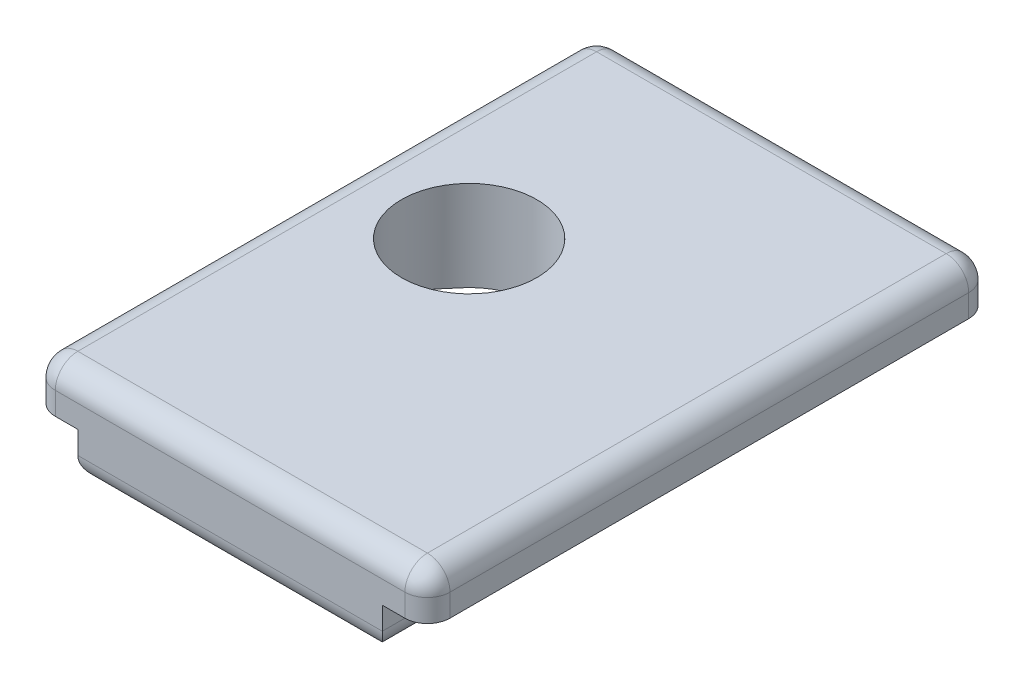
SolidWorks part; units mm, degrees
ref_plane "Front Plane" through (0, 0, 0) normal (0, 0, 1) x (1, 0, 0)
ref_plane "Top Plane" through (0, 0, 0) normal (0, 1, 0) x (1, 0, 0)
ref_plane "Right Plane" through (0, 0, 0) normal (1, 0, 0) x (0, 0, -1)
sketch "Sketch1" plane through (0, 0, 0) normal (0, 1, 0) x (1, 0, 0)
  line L1 (8.75, -12.5) -> (-8.75, -12.5)
  line L2 (8.75, -12.5) -> (8.75, 12.5)
  line L3 (8.75, 12.5) -> (-8.75, 12.5)
  line L4 (-8.75, -12.5) -> (-8.75, 12.5)
  line L5 (8.75, -12.5) -> (-8.75, 12.5) construction
  line L6 (8.75, 12.5) -> (-8.75, -12.5) construction
  point P0 (0, 0)
  dimension "D1" = 17.5
  dimension "D2" = 25
extrude "Boss-Extrude1" add sketch "Sketch1" along normal blind 2
sketch "Sketch2" plane through (0, 0, 0) normal (0, -1, 0) x (1, 0, 0)
  line L0 (-8.75, 12.5) -> (8.75, 12.5) construction
  line L1 (-6.75, 12.5) -> (6.75, 12.5)
  line L2 (-6.75, 12.5) -> (-6.75, -10.5)
  line L3 (-6.75, -10.5) -> (6.75, -10.5)
  line L4 (6.75, 12.5) -> (6.75, -10.5)
  line L5 (8.75, -12.5) -> (-8.75, -12.5) construction
  dimension "D1" = 6.75
  dimension "D2" = 6.75
  dimension "D3" = 2
extrude "Boss-Extrude2" add sketch "Sketch2" along normal blind 2
sketch "Sketch3" plane through (0, 2, 0) normal (0, 1, 0) x (1, 0, 0)
  line L1 (8.75, 12.5) -> (-8.75, 12.5) construction
  line L3 (8.75, -12.5) -> (8.75, 12.5) construction
  circle A0 centre (-3.4, 1.5) radius 3
  dimension "D1" = 6
  dimension "D2" = 11
  dimension "D3" = 12.15
extrude "Cut-Extrude1" cut sketch "Sketch3" against normal through all
fillet "Fillet1" radius 1 12 edges at (8.75, 1, -12.5) (0, 2, -12.5) (-8.75, 1, -12.5) (0, 2, 12.5) (8.75, 2, 0) (-8.75, 2, 0) (6.75, -2, 1) (0, -2, -10.5) (-6.75, -2, 1) (0, -2, 12.5) (8.75, 1, 12.5) (-8.75, 1, 12.5)
